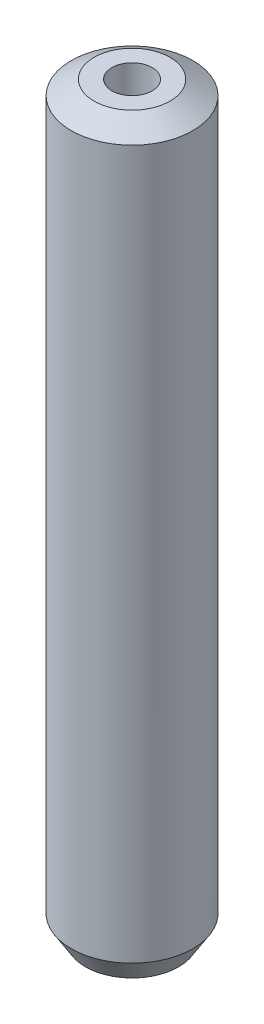
SolidWorks part; units mm, degrees
ref_plane "Front Plane" through (0, 0, 0) normal (0, 0, 1) x (1, 0, 0)
ref_plane "Top Plane" through (0, 0, 0) normal (0, 1, 0) x (1, 0, 0)
ref_plane "Right Plane" through (0, 0, 0) normal (1, 0, 0) x (0, 0, -1)
sketch "Sketch1" plane through (0, 0, 0) normal (0, 1, 0) x (1, 0, 0)
  circle A0 centre (0, 0) radius 12.5
  dimension "SHAFT_OD" = 25
extrude "Boss-Extrude1" add sketch "Sketch1" along normal blind 153.2732
sketch "Sketch2" plane through (0, 0, 0) normal (0, 1, 0) x (1, 0, 0)
  circle A0 centre (0, 0) radius 4.1443
  dimension "BORE_D" = 8.2886
extrude "Cut-Extrude1" cut sketch "Sketch2" along normal through all
chamfer "Chamfer1" distance 2.9151 angle 58.158 2 edges at (0, 153.2732, 12.5) (0, 0, 12.5) first distance on face at (0, 153.2732, 12.5) first distance on face at (0, 0, 4.1443)
